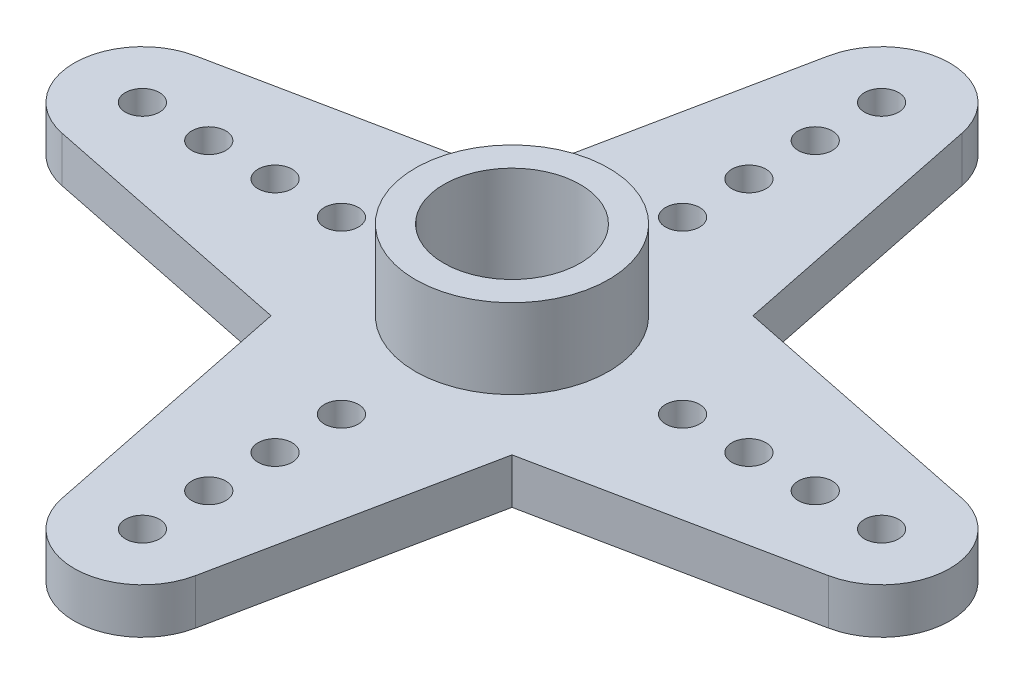
SolidWorks part; units mm, degrees
ref_plane "Front" through (0, 0, 0) normal (0, 0, 1) x (1, 0, 0)
ref_plane "Top" through (0, 0, 0) normal (0, 1, 0) x (1, 0, 0)
ref_plane "Right" through (0, 0, 0) normal (1, 0, 0) x (0, 0, -1)
sketch "Эскиз1" plane through (0, 0, 0) normal (0, 1, 0) x (1, 0, 0)
  line L0 (-16.25, 0) -> (16.25, 0) construction
  line L1 (0, 16.25) -> (0, -16.25) construction
  line L2 (-15.5, 0) -> (-14.0833, 0)
  line L3 (-12.5833, 0) -> (-11.1667, 0)
  line L4 (-9.6667, 0) -> (-8.25, 0)
  line L5 (0, 8.25) -> (0, 9.6667)
  line L6 (0, 11.1667) -> (0, 12.5833)
  line L7 (0, 14.0833) -> (0, 15.5)
  line L8 (-16.85, 2.9394) -> (-1.25, 6.1237)
  line L9 (-2.9394, 16.85) -> (-6.1237, 1.25)
  line L10 (2.9394, 16.85) -> (6.1237, 1.25)
  line L11 (1.25, 6.1237) -> (16.85, 2.9394)
  line L12 (16.85, -2.9394) -> (1.25, -6.1237)
  line L13 (-16.85, -2.9394) -> (-1.25, -6.1237)
  line L14 (-2.9394, -16.85) -> (-6.1237, -1.25)
  line L15 (2.9394, -16.85) -> (6.1237, -1.25)
  circle A0 centre (0, 0) radius 1.5
  circle A1 centre (0, 0) radius 4.25
  circle A2 centre (0, 0) radius 3
  circle A3 centre (0, 16.25) radius 0.75
  circle A4 centre (0, -16.25) radius 0.75
  circle A5 centre (16.25, 0) radius 0.75
  circle A6 centre (-16.25, 0) radius 0.75
  circle A7 centre (0, 13.3333) radius 0.75
  circle A8 centre (0, -13.3333) radius 0.75
  circle A9 centre (-13.3333, 0) radius 0.75
  circle A10 centre (13.3333, 0) radius 0.75
  circle A11 centre (10.4167, 0) radius 0.75
  circle A12 centre (0, 10.4167) radius 0.75
  circle A13 centre (-10.4167, 0) radius 0.75
  circle A14 centre (0, -10.4167) radius 0.75
  circle A15 centre (0, -7.5) radius 0.75
  circle A16 centre (-7.5, 0) radius 0.75
  circle A17 centre (0, 7.5) radius 0.75
  circle A18 centre (7.5, 0) radius 0.75
  circle A19 centre (0, 0) radius 6.25
  circle A20 centre (-16.25, 0) radius 3
  circle A21 centre (16.25, 0) radius 3
  circle A22 centre (0, -16.25) radius 3
  circle A23 centre (0, 16.25) radius 3
  dimension "D1" = 3
  dimension "D2" = 6
  dimension "D3" = 8.5
  dimension "D6" = 1.5
  dimension "D9" = 12.5
  dimension "D10" = 6
  dimension "D4" = 32.5
  dimension "D5" = 32.5
  dimension "D7" = 15
  dimension "D8" = 15
extrude "Бобышка-Вытянуть1" add sketch "Эскиз1" along normal blind 2 contours A20 A9 A13 A16 L13 L14 A19 L9 L8 | A9 A20 A6 | A21 L11 L10 A19 L15 L12 A10 A11 A18 | A21 A10 A5 | A7 A23 A3 | A23 A7 A12 A17 L9 L8 A19 L11 L10 | A19 L10 L11 | A19 L8 L9 | A19 L14 L13 | A19 L12 L15 | A22 L15 L12 A19 L13 L14 A8 A14 A15 | A22 A8 A4 | A19 A1 region at (-13.9279, 0, 0.5852) region at (-14.5775, 0, -2.6773) region at (-3.9649, 0, -11.0424) region at (-4.6135, 0, -4.6135) region at (-4.6135, 0, 4.6135) region at (-3.3051, 0, 5.8642) region at (0, 0, -6.0732) region at (0, 0, -19.1658) region at (-2.4729, 0, 14.7051) region at (4.6135, 0, -4.6135) region at (4.6135, 0, 4.6135) region at (11.0424, 0, -3.9649) region at (18.5086, 0, -1.8441)
extrude "Бобышка-Вытянуть2" add sketch "Эскиз1<3>" along normal blind 1 separate body contours A2 A0 region at (-2.9151, 0, 0)
sketch "Эскиз1<3>" plane through (0, 0, 0) normal (0, 1, 0) x (1, 0, 0) same geometry as "Эскиз1"
extrude "Бобышка-Вытянуть3" add sketch "Эскиз1<4>" along normal blind 5.5 contours A1 A2 region at (-4.1298, 0, 0)
sketch "Эскиз1<4>" plane through (0, 0, 0) normal (0, 1, 0) x (1, 0, 0) same geometry as "Эскиз1"
